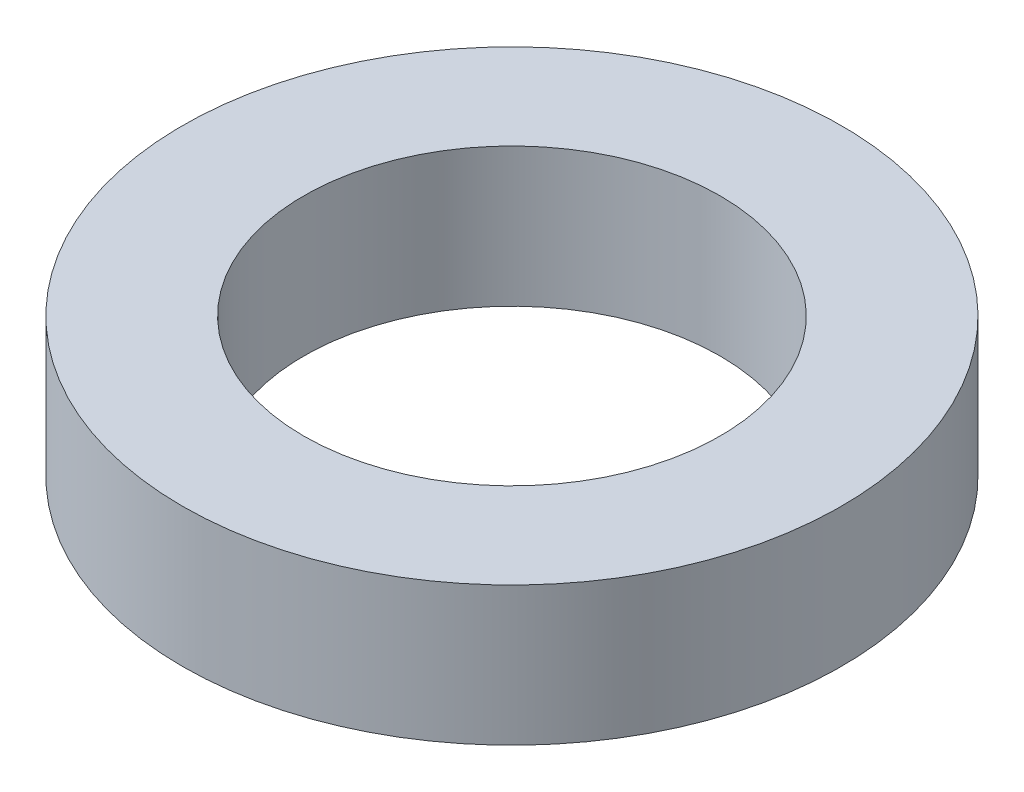
SolidWorks part; units mm, degrees
ref_plane "Front Plane" through (0, 0, 0) normal (0, 0, 1) x (1, 0, 0)
ref_plane "Top Plane" through (0, 0, 0) normal (0, 1, 0) x (1, 0, 0)
ref_plane "Right Plane" through (0, 0, 0) normal (1, 0, 0) x (0, 0, -1)
sketch "Sketch1" plane through (0, 0, 0) normal (0, 1, 0) x (1, 0, 0)
  circle A0 centre (0, 0) radius 47.5
  dimension "FLANGE_OD" = 95
extrude "Boss-Extrude1" add sketch "Sketch1" along normal blind 20
sketch "Sketch2" plane through (0, 0, 0) normal (0, 1, 0) x (1, 0, 0)
  circle A0 centre (0, 0) radius 30
  dimension "BORE_D" = 60
extrude "Cut-Extrude1" cut sketch "Sketch2" along normal through all
sketch "Sketch3" plane through (0, 20, 0) normal (0, 1, 0) x (1, 0, 0)
  circle A0 centre (0, 0) radius 18.2489 construction
  circle A1 centre (-18.2489, 0) radius 1.5495
  dimension "BOLT_D" = 3.099
  dimension "BOLT_PCD" = 36.4977
extrude "Cut-Extrude2" cut sketch "Sketch3" against normal blind 15.4939 rebuild error yes
pattern_circular "CirPattern1" count 8 over 360 rebuild error yes
